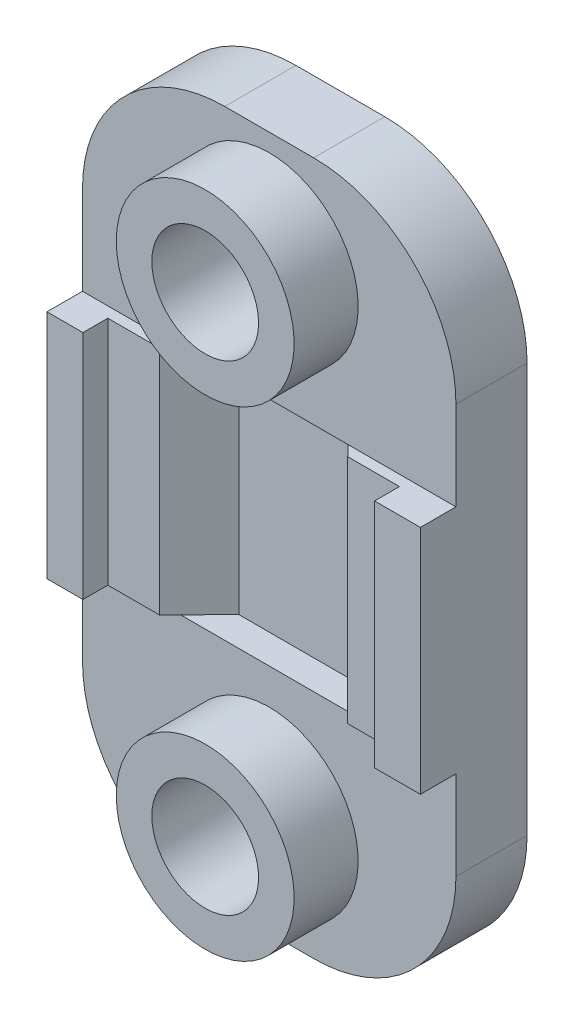
SolidWorks part; units mm, degrees
ref_plane "Front Plane" through (0, 0, 0) normal (0, 0, 1) x (1, 0, 0)
ref_plane "Top Plane" through (0, 0, 0) normal (0, 1, 0) x (1, 0, 0)
ref_plane "Right Plane" through (0, 0, 0) normal (1, 0, 0) x (0, 0, -1)
sketch "Szkic3" plane through (0, 0, 0) normal (0, 1, 0) x (1, 0, 0)
  line L0 (7.9238, -2) -> (7.9238, -0.6)
  line L1 (7.9238, -0.6) -> (5.0161, -0.6)
  line L2 (5.0161, -0.6) -> (2.8078, 1.65)
  line L3 (2.8078, 1.65) -> (-3.3601, 1.65)
  line L4 (-3.3601, 1.65) -> (-5.5684, -0.6)
  line L5 (-5.5684, -0.6) -> (-8.4762, -0.6)
  line L6 (-8.4762, -0.6) -> (-8.4762, -2)
  line L7 (-8.4762, -2) -> (-10.5, -2)
  line L8 (-10.5, -2) -> (-10.5, 2)
  line L9 (-10.5, 2) -> (10.5, 2)
  line L10 (10.5, 2) -> (10.5, -2)
  line L11 (10.5, -2) -> (7.9238, -2)
  dimension "D1" = 4
  dimension "D2" = 21
extrude "Dodanie-wyciągnięcie4" add sketch "Szkic3" along normal blind 13
sketch "Szkic4" plane through (0, 0, -2) normal (0, 0, -1) x (-1, 0, 0)
  line L1 (-10.5, 13) -> (10.5, 13)
  line L2 (-10.5, 13) -> (-10.5, 0)
  line L3 (-10.5, 0) -> (10.5, 0)
  line L4 (10.5, 13) -> (10.5, 0)
extrude "Dodanie-wyciągnięcie5" add sketch "Szkic4" along normal blind 2
sketch "Szkic5" plane through (0, 0, -4) normal (0, 0, -1) x (-1, 0, 0)
  line L0 (-10.5, 6.5) -> (-12.66, 6.5)
  line L1 (-10.5, 13) -> (10.5, 13)
  line L2 (-10.5, 13) -> (-10.5, 16)
  line L3 (-10.5, 16) -> (10.5, 16)
  line L4 (10.5, 13) -> (10.5, 16)
  line L9 (-10.5, 13) -> (-10.5, 0) construction
  line L14 (10.5, 0) -> (10.5, -3)
  line L15 (-10.5, -3) -> (10.5, -3)
  line L16 (-10.5, 0) -> (-10.5, -3)
  line L17 (-10.5, 0) -> (10.5, 0)
  line L18 (10.5, 16) -> (10.5, 26)
  line L19 (-10.5, -3) -> (10.5, -3)
  line L20 (-10.5, -3) -> (-10.5, -13)
  line L21 (-10.5, -13) -> (10.5, -13)
  line L22 (10.5, -3) -> (10.5, -13)
  line L23 (-10.5, 26) -> (10.5, 26)
  line L24 (-10.5, 16) -> (-10.5, 26)
  line L25 (-10.5, 16) -> (10.5, 16)
  line L26 (-10.5, 16) -> (10.5, 16)
  circle A0 centre (0, 20) radius 3
  circle A1 centre (0, 20) radius 5
  circle A4 centre (0, -7) radius 5
  circle A5 centre (0, -7) radius 3
  circle A6 centre (0, 20) radius 3
  line M8 (-10.5, 0) -> (10.5, 0)
  line M10 (10.5, 13) -> (-10.5, 13)
  dimension "D3" = 10
  dimension "D4" = 6
  dimension "D2" = 6
  dimension "D1" = 3
  dimension "D5" = 7
extrude "Dodanie-wyciągnięcie6" add sketch "Szkic5" against normal blind 4 contours A1 L3 L2 L4 M10 | L3 A1 A0 | L3 A1 | A4 L15 A5 | A4 L15 | L15 A4 L14 L16 M8 | L15 A4 L20 L21 L22 | A1 L3 L18 L23 L24 region at (0, 14.4239, -4) region at (10.2674, 21, -4) region at (2.1759, 24.3518, -4) region at (0, 15.5964, -4) region at (0, -1.4239, -4) region at (-10.2674, -8, -4) region at (-4.3518, -4.8241, -4) region at (0, -2.5964, -4)
extrude "Dodanie-wyciągnięcie7" add sketch "Szkic5<4>" against normal blind 3.6 from surface contours L26 A1 | L26 A1 A0 | A4 L19 | A4 L19 A5 region at (2.1759, 24.3518, -4) region at (0, 15.5964, -4) region at (-4.3518, -4.8241, -4) region at (0, -2.5964, -4) starting at face at (-0.0921, 17.3333, 0)
sketch "Szkic5<4>" plane through (0, 0, -4) normal (0, 0, -1) x (-1, 0, 0) same geometry as "Szkic5"
fillet "Zaokrąglenie3" radius 8 4 edges at (-10.5, -13, -2) (-10.5, 26, -2) (10.5, 26, -2) (10.5, -13, -2)
